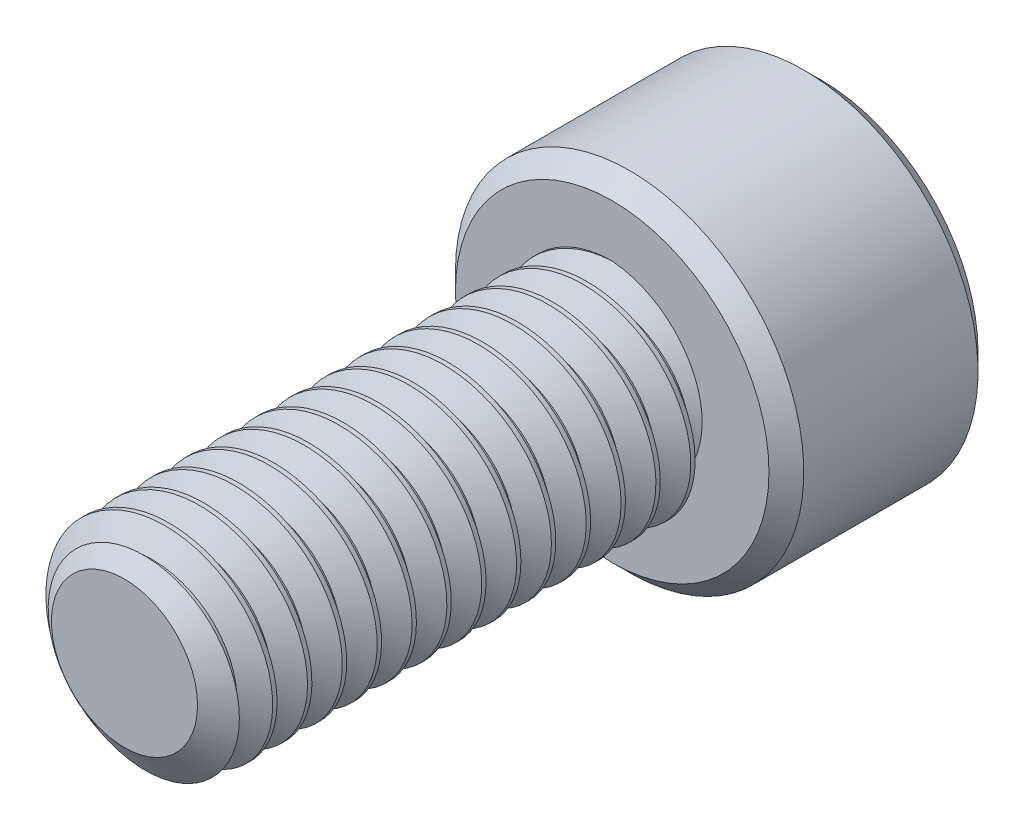
SolidWorks part; units mm, degrees
note: '?' marks a value the reader was unsure of.
other "DetailItem1"
ref_plane "Front Plane" through (0, 0, 0) normal (0, 0, 1) x (1, 0, 0)
ref_plane "Top Plane" through (0, 0, 0) normal (0, 1, 0) x (1, 0, 0)
ref_plane "Right Plane" through (0, 0, 0) normal (1, 0, 0) x (0, 0, -1)
sketch "Sketch1" plane through (0, 0, 0) normal (0, 0, 1) x (1, 0, 0)
  circle A0 centre (0, 0) radius 3
  dimension "OD" = 6
extrude "Extrude1" add sketch "Sketch1" against normal blind 14
sketch "Sketch2" plane through (0, 0, 0) normal (0, 0, 1) x (1, 0, 0)
  circle A0 centre (0, 0) radius 3 construction
  circle A1 centre (0, 0) radius 3
curve "Helix/Spiral1" pitch 1 height 15 turns 15 parameters "pitch"=1
sketch "Sketch3" plane through (0, 0, 0) normal (1, 0, 0) x (0, 0, -1)
  line L0 (-0.875, 3) -> (-0.5, 2.3505)
  line L1 (-0.5, 2.3505) -> (-0.375, 2.3505)
  line L2 (-0.375, 2.3505) -> (0, 3)
  line L3 (-0.875, 3) -> (0, 3)
  line L4 (-0.4375, 3) -> (-0.4375, 2.3505) construction
  line L5 (-0.6875, 2.6752) -> (-0.1875, 2.6752) construction
  line L6 (0, 3) -> (0, -3) construction
  dimension "D1" = 0.125
  dimension "D2" = 0.5
  dimension "D3" = 60
sweep "Cut-Sweep1" cut profiles "Sketch3" path "Helix/Spiral1"
sketch "Sketch4" plane through (0, 0, 0) normal (1, 0, 0) x (0, 0, -1)
  line L0 (0.6327, 3) -> (0, 2.0965)
  line L1 (0, 2.0965) -> (0, 3)
  line L2 (0.6327, 3) -> (0, 3)
  line L3 (-0.875, 3) -> (0, 3) construction
  line L4 (0, 0) -> (7.0209, 0) construction
  dimension "D1" = 55
  dimension "D2" = 0.254
revolve "Cut-Revolve1" cut sketch "Sketch4" angle 360 about L4
sketch "Sketch6" plane through (0, 0, -14) normal (0, 0, -1) x (-1, 0, 0)
  circle A0 centre (0, 0) radius 5
  dimension "head dia" = 10
extrude "Extrude2" add sketch "Sketch6" along normal blind 6
sketch "Sketch7" plane through (0, 0, -20) normal (0, 0, -1) x (-1, 0, 0)
  line L1 (0, 2.8868) -> (-2.5, 1.4434)
  line L2 (-2.5, 1.4434) -> (-2.5, -1.4434)
  line L3 (-2.5, -1.4434) -> (0, -2.8868)
  line L4 (0, -2.8868) -> (2.5, -1.4434)
  line L5 (2.5, -1.4434) -> (2.5, 1.4434)
  line L6 (2.5, 1.4434) -> (0, 2.8868)
  circle A0 centre (0, 0) radius 2.5 construction
  dimension "hex dia" = 5
extrude "Cut-Extrude1" cut sketch "Sketch7" against normal blind 3.75
sketch "Sketch8" plane through (0, 0, -20) normal (0, 0, -1) x (-1, 0, 0)
  circle A0 centre (0, 0) radius 2.8868
extrude "Cut-Extrude2" cut sketch "Sketch8" against normal through all draft 45
chamfer "Chamfer1" distance 0.5 angle 45 2 edges at (-5, 0, -20) (-5, 0, -14)
sketch "Sketch10" plane through (0, 0, -14) normal (0, 0, 1) x (1, 0, 0)
  circle A1 centre (0, 0) radius 3
  circle A2 centre (0, 0) radius 3
  dimension "D1" = 0
ref_plane "Plane1" through (0, 0, 0) normal (0, 0, 1) x (1, 0, 0)
extrude "partial thread" [suppressed] add sketch "Sketch10" along normal up to surface (31 mm away) separate body
chamfer "Chamfer2" [suppressed] distance 0.12 angle 45
combine bodies "Combine1" [suppressed] operation type? add bodies to combine 107 108
sketch "Sketch9" plane through (0, 0, 0) normal (1, 0, 0) x (0, 0, -1)
  line L0 (0, 3) -> (0, -3) construction
  line L1 (2.5, 3) -> (2.5, -3) construction
  dimension "D1" = 2.5
equation "\"D3@Helix/Spiral1\" = \"screw length@Extrude1\"+\"pitch@Helix/Spiral1\""
equation "\"D1@Sketch3\" = \"pitch@Helix/Spiral1\"*.125"
equation "\"D2@Sketch3\" = \"pitch@Helix/Spiral1\"*.5"
equation "\"D1@Cut-Extrude1\" = \"hex dia@Sketch7\"*.75"
equation "\"D1@Chamfer1\" = \"head dia@Sketch6\"*.05"
equation "\"D1@Sketch9\" = \"pitch@Helix/Spiral1\"*2.5"
equation "\"D1@Chamfer2\"=\"OD@Sketch1\"*.02"
